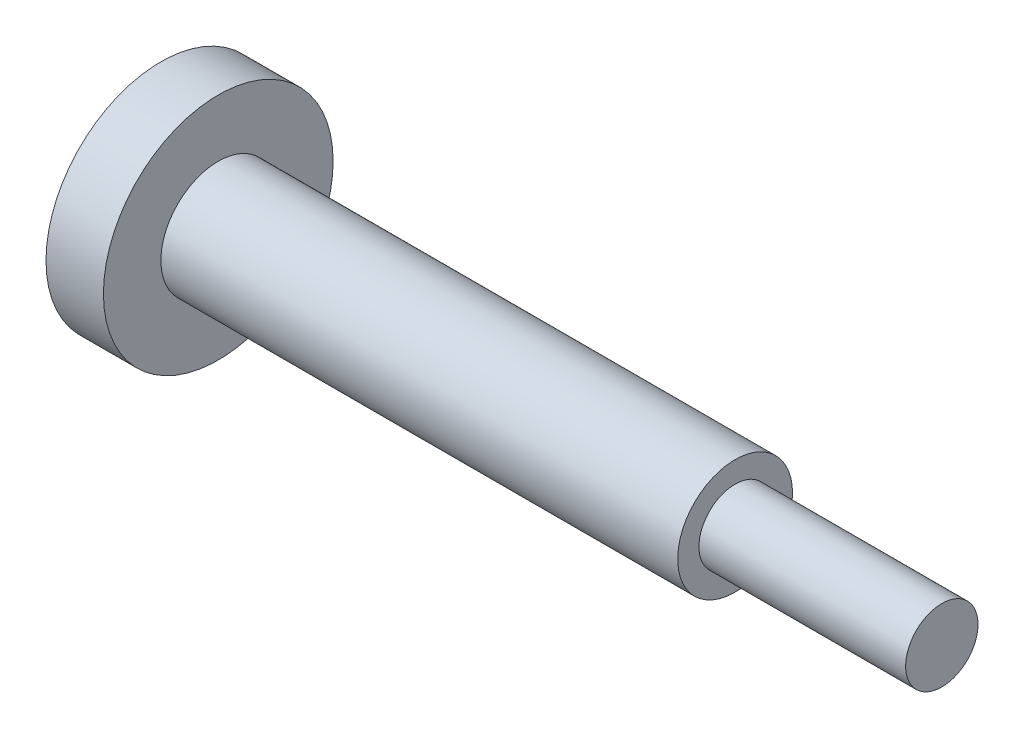
SolidWorks part; units mm, degrees
ref_plane "Front Plane" through (0, 0, 0) normal (0, 0, 1) x (1, 0, 0)
ref_plane "Top Plane" through (0, 0, 0) normal (0, 1, 0) x (1, 0, 0)
ref_plane "Right Plane" through (0, 0, 0) normal (1, 0, 0) x (0, 0, -1)
sketch "Sketch1" plane through (0, 0, 0) normal (1, 0, 0) x (0, 0, -1)
  circle A0 centre (0, 0) radius 3.175
  circle A1 centre (0, 0) radius 2
  dimension "D1" = 6.35
  dimension "D2" = 4
extrude "Boss-Extrude1" add sketch "Sketch1" along normal blind 11.43 contours A0 | A1 region at (0, 0, 0)
extrude "Boss-Extrude2" add sketch "Sketch1<3>" against normal blind 28.575 contours A0 | A1 region at (0, 0, 3.0852) region at (0, 0, 0)
sketch "Sketch1<3>" plane through (0, 0, 0) normal (1, 0, 0) x (0, 0, -1) same geometry as "Sketch1"
sketch "Sketch2" plane through (-28.575, 0, 0) normal (-1, 0, 0) x (0, 0, 1)
  circle A0 centre (0, 0) radius 6.35
  dimension "D1" = 12.7
extrude "Boss-Extrude3" add sketch "Sketch2" along normal blind 3.175
